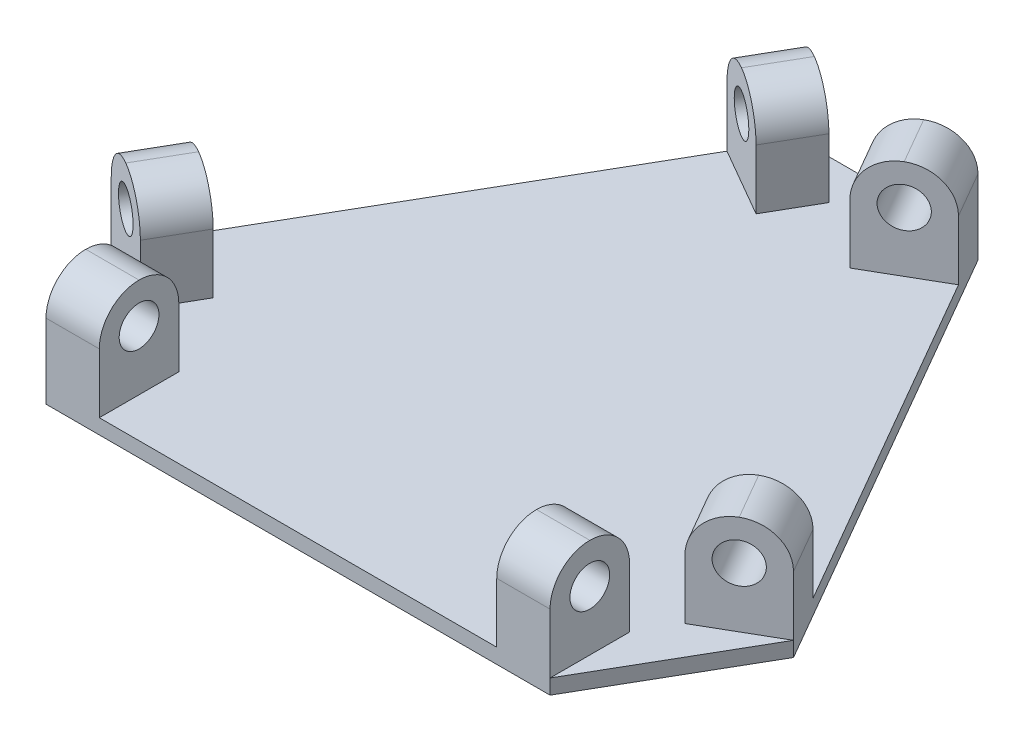
SolidWorks part; units mm, degrees
ref_plane "Front Plane" through (0, 0, 0) normal (0, 0, 1) x (1, 0, 0)
ref_plane "Top Plane" through (0, 0, 0) normal (0, 1, 0) x (1, 0, 0)
ref_plane "Right Plane" through (0, 0, 0) normal (1, 0, 0) x (0, 0, -1)
sketch "Sketch3" plane through (0, 0, 0) normal (0, 1, 0) x (1, 0, 0)
  line L0 (-8.9683, 34.4665) -> (8.9683, 34.4665)
  line L1 (0, 0) -> (21.6506, 12.5) construction
  line L2 (0, 0) -> (0, -25) construction
  line L3 (0, 0) -> (-21.6506, 12.5) construction
  line L7 (8.9683, 34.4665) -> (34.333, -9.4665)
  line L8 (34.333, -9.4665) -> (25.3647, -25)
  line L9 (25.3647, -25) -> (-25.3647, -25)
  line L10 (-25.3647, -25) -> (-34.333, -9.4665)
  line L11 (-34.333, -9.4665) -> (-8.9683, 34.4665)
  circle A0 centre (0, 0) radius 25 construction
  dimension "D1" = 120
  dimension "D3" = 50
  dimension "D2" = 120
extrude "Boss-Extrude2" add sketch "Sketch3" along normal blind 1.5
sketch "Sketch7" plane through (0, 1.5, 0) normal (0, 1, 0) x (1, 0, 0)
  circle A0 centre (0, 0) radius 25 construction
ref_axis "Axis1" through (0, 1.5, 0) along (0, -1, 0)
sketch "Sketch4" plane through (0, 1.5, 0) normal (0, 1, 0) x (1, 0, 0)
  line L0 (-25.3647, -17) -> (-25.3647, -25)
  line L2 (-25.3647, -25) -> (-20, -25)
  line L3 (-20, -25) -> (-20, -17)
  line L4 (-20, -17) -> (-25.3647, -17)
  line L5 (20, -25) -> (20, -17)
  line L6 (20, -17) -> (25.3647, -17)
  line L7 (25.3647, -17) -> (25.3647, -25)
  line L8 (25.3647, -25) -> (20, -25)
  line L9 (-20, -21) -> (20, -21) construction
  line L10 (0, -21) -> (0, -25) construction
  line L11 (-25.3647, -25) -> (25.3647, -25) construction
  dimension "D1" = 40
  dimension "D2" = 4
extrude "Boss-Extrude3" add sketch "Sketch4" along normal blind 10
sketch "Sketch5" plane through (25.3647, 0, 0) normal (1, 0, 0) x (0, 0, -1)
  line L0 (-21, 7.5) -> (-25, 7.5) construction
  line L3 (-21, 11.5) -> (-21, 7.5) construction
  line L4 (-25, 11.5) -> (-17, 11.5) construction
  line L6 (-25, 11.5) -> (-25, 1.5) construction
  circle A0 centre (-21, 7.5) radius 2
  dimension "D1" = 4
extrude "Cut-Extrude2" cut sketch "Sketch5" against normal through all
fillet "Fillet1" radius 4 4 edges at (-22.6823, 11.5, 17) (-22.6823, 11.5, 25) (22.6823, 11.5, 17) (22.6823, 11.5, 25)
pattern_circular "CirPattern1" count 3 over 360 about axis through (0, 1.5, 0) along (0, -1, 0) of "Boss-Extrude3", "Fillet1", "Cut-Extrude2"
